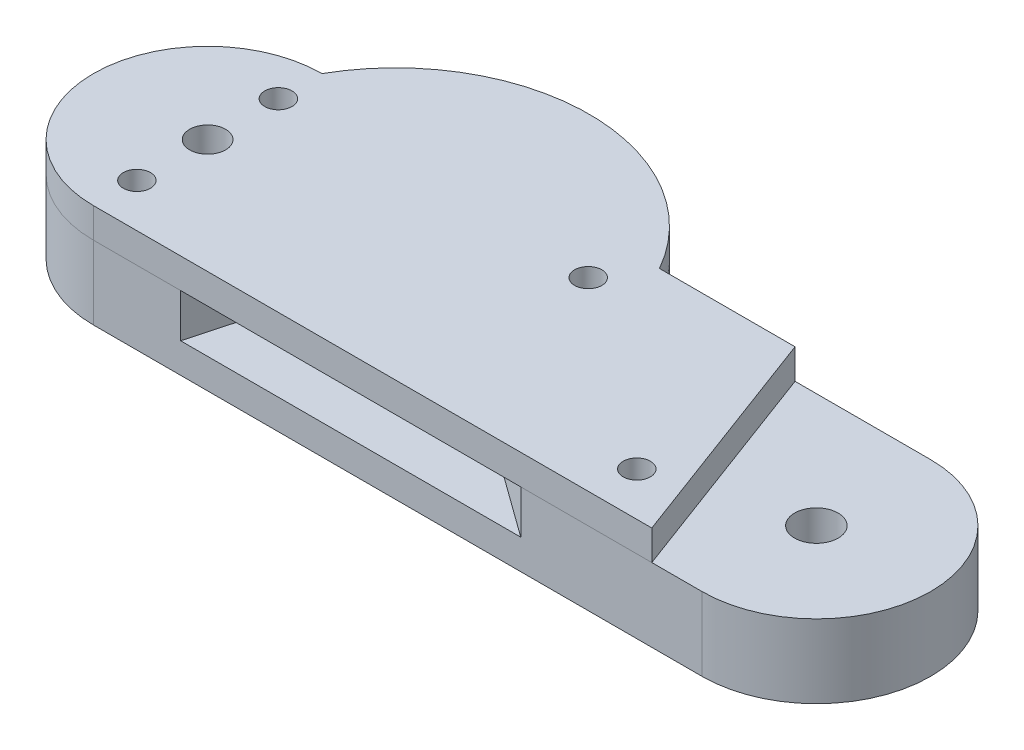
SolidWorks part; units mm, degrees
ref_plane "Front Plane" through (0, 0, 0) normal (0, 0, 1) x (1, 0, 0)
ref_plane "Top Plane" through (0, 0, 0) normal (0, 1, 0) x (1, 0, 0)
ref_plane "Right Plane" through (0, 0, 0) normal (1, 0, 0) x (0, 0, -1)
sketch "Sketch1" plane through (0, 0, 0) normal (0, 1, 0) x (1, 0, 0)
  line L0 (0, -10.5004) -> (-55.9305, -10.5004)
  line L1 (0, 10.5004) -> (-55.9305, 10.5004)
  line L5 (0, 11.5004) -> (-55.9305, 11.5004) construction
  line L6 (0, -11.5004) -> (-55.9305, -11.5004) construction
  circle A0 centre (0, 0) radius 2
  arc A1 (0, -10.5004) -> (0, 10.5004) centre (0, 0) ccw
  arc A2 (-55.9305, 10.5004) -> (-55.9305, -10.5004) centre (-55.9305, 0) ccw
  circle A3 centre (-55.9305, 0) radius 1.65
  arc A7 (0, -11.5004) -> (0, 11.5004) centre (0, 0) ccw construction
  arc A8 (-55.9305, 11.5004) -> (-55.9305, -11.5004) centre (-55.9305, 0) ccw construction
  arc A9 (-67.2423, -5.04) -> (-54.9145, -15.6487) centre (-55.7741, -4.1805) ccw construction
  arc A10 (-55.9305, 10.5004) -> (-55.9305, -10.5004) centre (-55.9305, 0) ccw construction
  circle A11 centre (0, 0) radius 67.4309 construction
  arc A12 (-59.8966, 30.973) -> (-67.2423, -5.04) centre (0, 0) ccw construction
  dimension "D1" = 4
  dimension "D2" = 1
  dimension "D3" = 3.3
extrude "Boss-Extrude1" add sketch "Sketch1" along normal mid plane 9.5
sketch "Sketch3" plane through (0, 0, 0) normal (0, 1, 0) x (1, 0, 0)
  line L0 (0, 0) -> (-47.1525, -15.3208) construction
  line L1 (0, 0) -> (24.7895, -42.9367) construction
  line L2 (0, 0) -> (-55.9305, 0) construction
  line L3 (24.7895, -42.9367) -> (-41.5934, 5.0595) construction
  line L4 (-41.5934, 5.0595) -> (-47.1525, -15.3208) construction
  line L5 (-41.5934, 5.0595) -> (-37.6461, 19.5308) construction
  line L6 (-41.5934, 5.0595) -> (-53.749, 13.8482) construction
  line L7 (22.8477, -44.0007) -> (-38.0092, 0) construction
  line L8 (-35.7518, 18.8753) -> (-39.2995, 5.869)
  line L9 (-43.8873, 4.25) -> (-54.8123, 12.149)
  line L11 (26.6452, -41.8104) -> (-39.2995, 5.869)
  line L12 (-39.6108, 19.9279) -> (-42.7627, 8.3729) construction
  line L13 (-42.7627, 8.3729) -> (-52.4686, 15.3905) construction
  line L14 (-40.9004, 0) -> (-45.9674, -18.5763) construction
  line L15 (-43.8873, 4.25) -> (-48.2065, -11.585)
  line L18 (-40.4216, 6.6802) -> (-50.8477, 14.2185) construction
  line L20 (-41.5934, 5.0595) -> (-52.0196, 12.5978) construction
  line L21 (-42.7652, 3.4387) -> (-53.1914, 10.977) construction
  line L23 (-43.5229, 5.5858) -> (-49.082, -14.7945) construction
  line L26 (-39.6639, 4.5332) -> (-45.223, -15.8471) construction
  line L27 (25.9613, -41.316) -> (-40.4216, 6.6802) construction
  line L28 (23.6177, -44.5574) -> (-42.7652, 3.4387) construction
  arc A1 (-48.2065, -11.585) -> (26.6452, -41.8104) centre (0, 0) ccw
  arc A4 (-55.9305, 10.5004) -> (-55.9305, -10.5004) centre (-55.9305, 0) ccw construction
  arc A7 (-35.7518, 18.8753) -> (-54.8123, 12.149) centre (-41.5934, 5.0595) ccw
  dimension "D1" = 99.1581
  dimension "D3" = 120
  dimension "D6" = 30
  dimension "D2" = 18
  dimension "D4" = 2
  dimension "D5" = 2
extrude "Cut-Extrude1" cut sketch "Sketch3" against normal mid plane 4
sketch "Sketch5" plane through (0, 0, 0) normal (0, 1, 0) x (1, 0, 0)
  line L0 (-40.4241, 1.7461) -> (-52.5322, 10.5004) construction
  line L1 (-40.4241, 1.7461) -> (-35.7382, 18.9254) construction
  line L2 (-52.5322, 10.5004) -> (-43.8873, 4.25) construction
  line L3 (-39.2995, 5.869) -> (-38.0362, 10.5004) construction
  line L4 (-55.9305, 10.5004) -> (-24.9177, 10.5004)
  line L5 (0, 10.5004) -> (-55.9305, 10.5004) construction
  circle A0 centre (-40.4241, 1.7461) radius 17.807
extrude "Boss-Extrude2" add sketch "Sketch5" along normal up to surface and the other way up to surface contours A0 region at (-40.4241, 0, -14.2141) up to face at (0, 4.75, 2) other way up to face at (-27.9653, -4.75, 0)
sketch "Sketch6" plane through (0, 0, 0) normal (0, 1, 0) x (1, 0, 0)
  line L0 (-39.2995, 5.869) -> (-16.6593, -10.5004)
  line L1 (-47.9107, -10.5004) -> (-43.8873, 4.25)
  line L2 (-43.8873, 4.25) -> (-54.8544, 12.1794)
  line L3 (-39.2995, 5.869) -> (-35.7382, 18.9254)
  line L4 (-16.6593, -10.5004) -> (-39.2995, 5.869) construction
  line L5 (-43.8873, 4.25) -> (-47.9107, -10.5004) construction
  line L6 (-52.5322, 10.5004) -> (-43.8873, 4.25) construction
  line L7 (-39.2995, 5.869) -> (-38.0362, 10.5004) construction
  line L8 (-55.9305, -10.5004) -> (0, -10.5004) construction
  line L9 (-16.6593, -10.5004) -> (-47.9107, -10.5004)
  arc A0 (-24.9177, 10.5004) -> (-55.9305, 10.5004) centre (-40.4241, 1.7461) ccw construction
  arc A1 (-35.7382, 18.9254) -> (-54.8544, 12.1794) centre (-40.4241, 1.7461) ccw
extrude "Cut-Extrude2" cut sketch "Sketch6" against normal mid plane 4
sketch "Sketch7" plane through (0, -4.75, 0) normal (0, -1, 0) x (1, 0, 0)
  line L0 (0, 0) -> (4.5965, 4.5965) construction
  line L1 (0, 0) -> (6.5004, 0) construction
  line L4 (0, 6.5004) -> (-55.9305, 6.5004)
  line L5 (-27.4616, -6.5004) -> (0, -6.5004)
  line L6 (0, 6.5004) -> (-55.9305, 6.5004) construction
  line L7 (-55.9305, -6.5004) -> (0, -6.5004) construction
  circle A3 centre (-27.4616, -6.5004) radius 1.25
  circle A4 centre (0, -6.5004) radius 1.25 construction
  circle A5 centre (4.5965, 4.5965) radius 1.25 construction
  arc A6 (0, -6.5004) -> (0, 6.5004) centre (0, 0) ccw
  arc A7 (-55.9305, 6.5004) -> (-53.5442, -6.0466) centre (-55.9305, 0) ccw
  arc A8 (-53.5442, -6.0466) -> (-27.4616, -6.5004) centre (-40.4241, -1.7461) ccw
  arc A9 (0, -6.5004) -> (0, 6.5004) centre (0, 0) ccw construction
  arc A10 (-55.9305, 6.5004) -> (-53.5442, -6.0466) centre (-55.9305, 0) ccw construction
  arc A11 (-53.5442, -6.0466) -> (-27.4616, -6.5004) centre (-40.4241, -1.7461) ccw construction
  circle A12 centre (-10, 6.5004) radius 1.25
  circle A13 centre (-55.9305, 6.5004) radius 1.25
  circle A14 centre (-55.9305, -6.5004) radius 1.25
  dimension "D4" = 2.5
  dimension "D2" = 10
  dimension "D3" = 45
  dimension "D1" = 4
extrude "Cut-Extrude3" cut sketch "Sketch7" against normal through all
sketch "Sketch8" plane through (0, -4.75, 0) normal (0, -1, 0) x (1, 0, 0)
  circle A0 centre (-55.9305, 6.5004) radius 2.75
  circle A1 centre (-55.9305, -6.5004) radius 2.75
  circle A2 centre (-27.4616, -6.5004) radius 2.75
  circle A3 centre (-10, 6.5004) radius 2.75
  dimension "D1" = 5.5
extrude "Cut-Extrude4" cut sketch "Sketch8" against normal blind 3.2
ref_plane "Plane1" through (0, 2, 0) normal (0, -1, 0) x (-1, 0, 0)
sketch "Sketch9" plane through (0, 4.75, 0) normal (0, 1, 0) x (1, 0, 0)
  line L0 (-12.4589, 10.5004) -> (-4.6195, -10.5004)
  line L1 (0, 10.5004) -> (-24.9177, 10.5004) construction
  line L2 (-55.9305, -10.5004) -> (0, -10.5004) construction
  line L3 (-6.5881, -5.2268) -> (-10, -6.5004) construction
  line L4 (-4.6195, -10.5004) -> (0, -10.5004)
  line L5 (-12.4589, 10.5004) -> (0, 10.5004)
  circle A0 centre (0, 0) radius 8 construction
  circle A1 centre (-10, -6.5004) radius 1.25 construction
  circle A2 centre (-10, -6.5004) radius 1.25 construction
  arc A3 (0, -10.5004) -> (0, 10.5004) centre (0, 0) ccw
  arc A4 (0, -10.5004) -> (0, 10.5004) centre (0, 0) ccw construction
  dimension "D1" = 16
extrude "Cut-Extrude5" cut sketch "Sketch9" against normal up to surface (2.75 mm away) up to face at (-39.9005, 2, -3.8681)
split "Split1" trim tools "Plane1" bodies to split 113 resulting bodies 111 112
